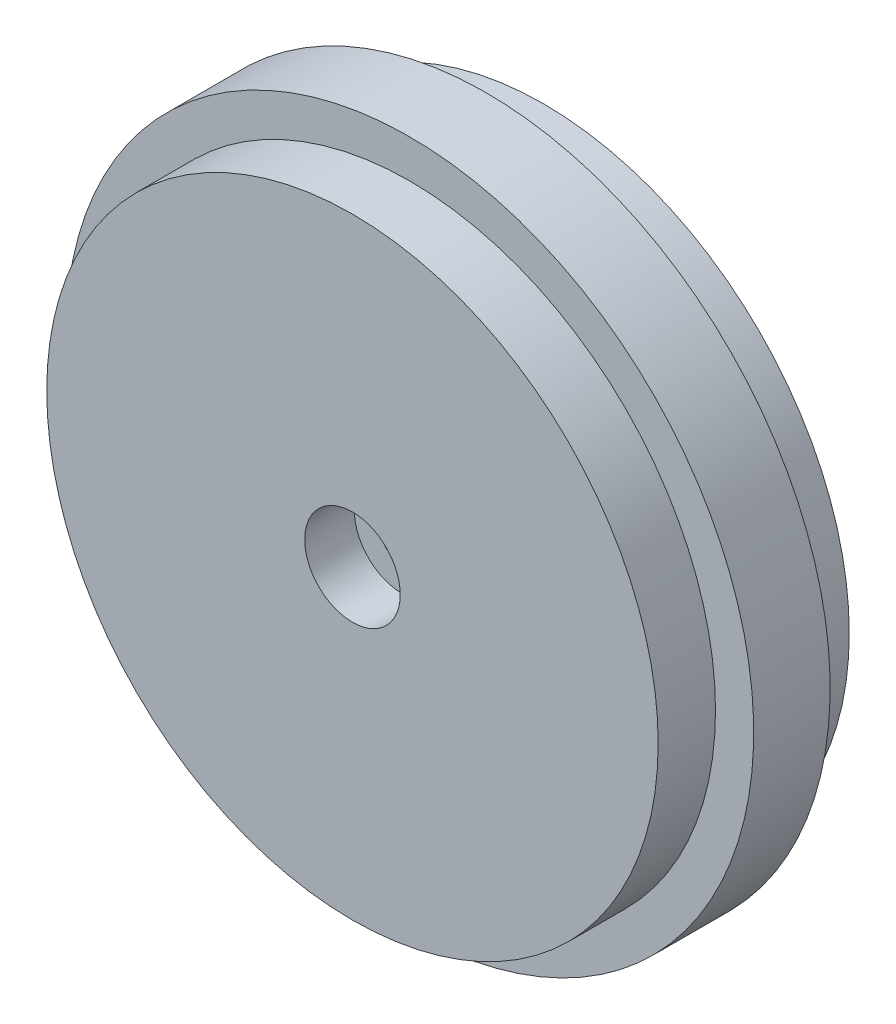
SolidWorks part; units mm, degrees
material "PET"
ref_plane "Plan de face" through (0, 0, 0) normal (0, 0, 1) x (1, 0, 0)
ref_plane "Plan de dessus" through (0, 0, 0) normal (0, 1, 0) x (1, 0, 0)
ref_plane "Plan de droite" through (0, 0, 0) normal (1, 0, 0) x (0, 0, -1)
sketch "Esquisse1" plane through (0, 0, 0) normal (0, 0, 1) x (1, 0, 0)
  circle A0 centre (0, 0) radius 14.5
  dimension "D1" = 29
extrude "Boss.-Extru.1" add sketch "Esquisse1" along normal blind 10
sketch "Esquisse2" plane through (0, 0, 0) normal (0, 0, 1) x (1, 0, 0)
  circle A0 centre (0, 0) radius 16.5
  dimension "D1" = 33
extrude "Boss.-Extru.2" add sketch "Esquisse2" along normal offset from surface (8 mm away) 1 from offset 1 up to face at (14.5, 0, 10)
sketch "Esquisse6" plane through (0, 0, 10) normal (0, 0, 1) x (1, 0, 0)
  circle A0 centre (0, 0) radius 13.5
  dimension "D1" = 27
extrude "Enlèv. mat.-Extru.4" cut sketch "Esquisse6" against normal blind 1
hole_wizard "Chambrage pour vis à tête ronde bombée M21" positions "Esquisse9" profile "Esquisse8" counterbore size "M2" standard "Ansi Metric" end condition through all
sketch "Esquisse9" plane through (0, 0, 9) normal (0, 0, 1) x (1, 0, 0)
  point P0 (0, 0)
sketch "Esquisse8" plane through (0, 0, 9) normal (1, 0, 0) x (0, -1, 0)
  line L0 (0, 0) -> (0, 9)
  line L1 (0, 9) -> (1.2, 9)
  line L3 (1.2, 9) -> (1.2, 1.6)
  line L4 (1.2, 1.6) -> (2.5, 1.6)
  line L5 (2.5, 1.6) -> (2.5, 0)
  line L7 (2.5, 0) -> (0, 0)
  line L11 (0, -6.35) -> (0, 107.95) construction
  dimension "Diamètre du perçage jusqu'au prochain" = 2.4
  dimension "Profondeur du perçage jusqu'au prochain" = 9
  dimension "Diamètre du chambrage" = 5
  dimension "Profondeur du chambrage" = 1.6
sketch "Esquisse13" plane through (0, 0, 0) normal (0, 0, -1) x (-1, 0, 0)
  circle A0 centre (0, 0) radius 13.5
  circle A1 centre (0, 0) radius 4.2
  dimension "D1" = 27
  dimension "D2" = 8.4
extrude "Enlèv. mat.-Extru.7" cut sketch "Esquisse13" against normal offset from surface (7 mm away) 2 up to face at (2.5, 0, 9)
sketch "Esquisse15" plane through (0, 0, 0) normal (0, 0, -1) x (-1, 0, 0)
  line L0 (-2.15, 2.0922) -> (-2.15, -2.0922)
  line L1 (2.15, 2.0922) -> (2.15, -2.0922)
  arc A0 (-2.15, -2.0922) -> (2.15, -2.0922) centre (0, 0) ccw
  arc A1 (2.15, 2.0922) -> (-2.15, 2.0922) centre (0, 0) ccw
  dimension "D1" = 6
  dimension "D2" = 2.15
  dimension "D3" = 2.15
extrude "Enlèv. mat.-Extru.8" cut sketch "Esquisse15" against normal blind 7
sketch "Sketch2" plane through (0, 0, 1) normal (0, 0, -1) x (-1, 0, 0)
  circle A0 centre (0, 0) radius 16.5
  circle A1 centre (0, 0) radius 14.5
extrude "Boss-Extrude2" add sketch "Sketch2" along normal up to surface (1 mm away) and the other way up to surface (9 mm away) up to face at (0, 0, 0) other way up to face at (13.5, 0, 10)
sketch "Sketch3" plane through (0, 0, 0) normal (0, 0, -1) x (-1, 0, 0)
  circle A0 centre (0, 0) radius 16.5
  circle A1 centre (0, 0) radius 22.5
  dimension "D1" = 6
extrude "Boss-Extrude3" add sketch "Sketch3" against normal up to surface (10 mm away) up to face at (13.5, 0, 10)
fillet "Fillet1" radius 1 2 edges at (-22.5, 0, 0) (22.5, 0, 10)
ref_plane "Plane1" through (0, 0, 0) normal (1, 0, 0) x (0, 0, -1)
sketch "Sketch4" plane through (0, 0, 0) normal (1, 0, 0) x (0, 0, -1)
  line L0 (-9, 22.5) -> (-1, 22.5) construction
  line L1 (-1, 22.5) -> (-9, 22.5) construction
  line L2 (-9, 22.5) -> (-9, 18)
  line L3 (-5, 22.5) -> (-5, 24.473) construction
  line L4 (-9, 18) -> (-1, 18)
  line L5 (-1, 18) -> (-1, 22.5)
  arc A0 (-9, 22.5) -> (-1, 22.5) centre (-5, 14.0611) cw
  point P10 (-5, 23.4)
  dimension "D2" = 0.9
extrude "Boss-Extrude4" add sketch "Sketch4" along normal blind 0.5 and the other way blind 0.5
pattern_circular "CirPattern1" count 70 over 360 about axis through (0, 0, 73.6396) along (0, 0, -1) of "Boss-Extrude4"
sketch "Sketch5" plane through (0, 0, 0) normal (0, 0, -1) x (-1, 0, 0)
  circle A0 centre (0, 0) radius 16
  circle A1 centre (0, 0) radius 40
  dimension "D1" = 32
  dimension "D2" = 80
extrude "Cut-Extrude1" cut sketch "Sketch5" against normal blind 20
sketch "Sketch6" plane through (0, 0, 0) normal (0, 0, -1) x (-1, 0, 0)
  circle A0 centre (0, 0) radius 16
  circle A1 centre (0, 0) radius 18
  circle A2 centre (0, 0) radius 16 construction
  dimension "D1" = 2
extrude "Boss-Extrude5" add sketch "Sketch6" against normal blind 4 from offset 3 offset against normal yes
sketch "Sketch8" plane through (0, 0, 9) normal (0, 0, 1) x (1, 0, 0)
  circle A0 centre (0, 0) radius 13.5
  circle A1 centre (0, 0) radius 2.5
  circle A2 centre (0, 0) radius 13.5 construction
  circle A3 centre (0, 0) radius 2.5 construction
extrude "Boss-Extrude6" add sketch "Sketch8" along normal up to surface (1 mm away) up to face at (13.5, 0, 10)
